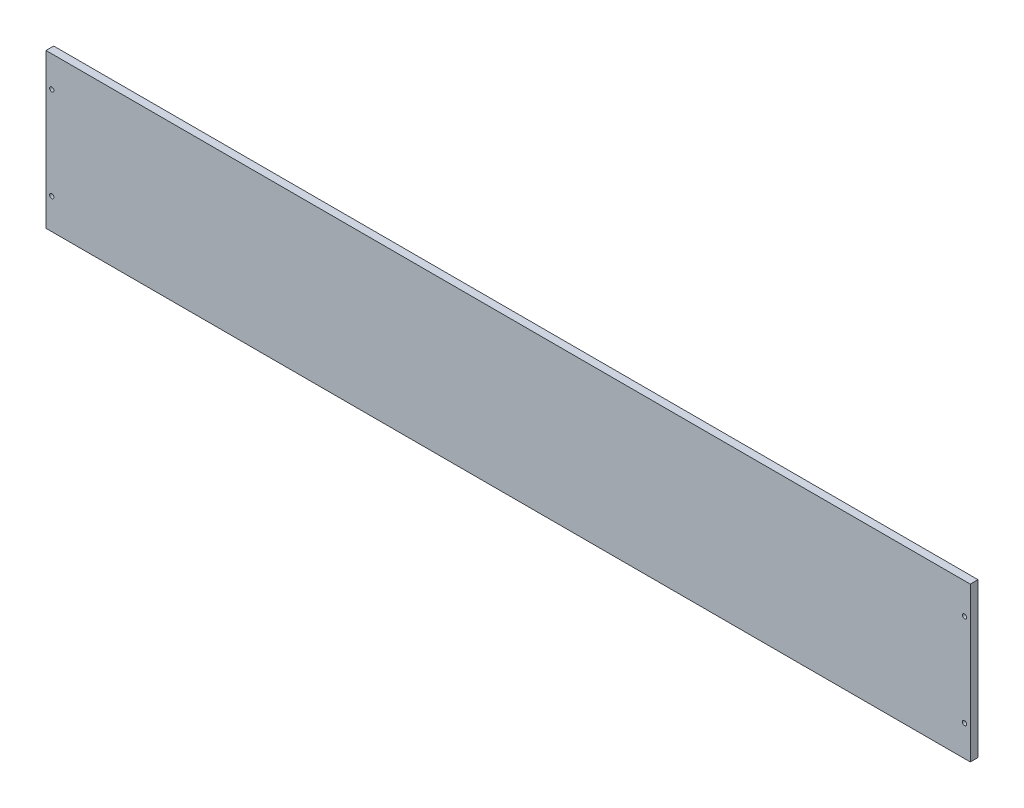
SolidWorks part; units mm, degrees
ref_plane "Plan de face" through (0, 0, 0) normal (0, 0, 1) x (1, 0, 0)
ref_plane "Plan de dessus" through (0, 0, 0) normal (0, 1, 0) x (1, 0, 0)
ref_plane "Plan de droite" through (0, 0, 0) normal (1, 0, 0) x (0, 0, -1)
sketch "Esquisse1" plane through (0, 0, 0) normal (0, 0, 1) x (1, 0, 0)
  line L1 (0, 0) -> (1200, 0)
  line L2 (0, 0) -> (0, -200)
  line L3 (0, -200) -> (1200, -200)
  line L4 (1200, 0) -> (1200, -200)
  dimension "D1" = 200
  dimension "D2" = 1200
extrude "Boss.-Extru.1" add sketch "Esquisse1" along normal blind 10
sketch "Esquisse2" plane through (0, 0, 10) normal (0, 0, 1) x (1, 0, 0)
  line L0 (0, 0) -> (0, -200) construction
  line L1 (1200, -200) -> (1200, 0) construction
  line L2 (1200, 0) -> (0, 0) construction
  line L3 (0, -200) -> (1200, -200) construction
  circle A0 centre (7.5, -40) radius 2.75
  circle A1 centre (7.5, -160) radius 2.75
  circle A2 centre (1192.5, -40) radius 2.75
  circle A3 centre (1192.5, -160) radius 2.75
  dimension "D5" = 5.5
  dimension "D6" = 5.5
  dimension "D7" = 5.5
  dimension "D8" = 5.5
  dimension "D1" = 7.5
  dimension "D2" = 7.5
  dimension "D3" = 7.5
  dimension "D4" = 7.5
  dimension "D9" = 40
  dimension "D10" = 40
  dimension "D11" = 40
  dimension "D12" = 40
extrude "Enlèv. mat.-Extru.1" cut sketch "Esquisse2" against normal blind 10
chamfer "Chanfrein1" distance 2.5 angle 45 4 edges at (10.25, -160, 0) (10.25, -40, 0) (1195.25, -40, 0) (1195.25, -160, 0)
